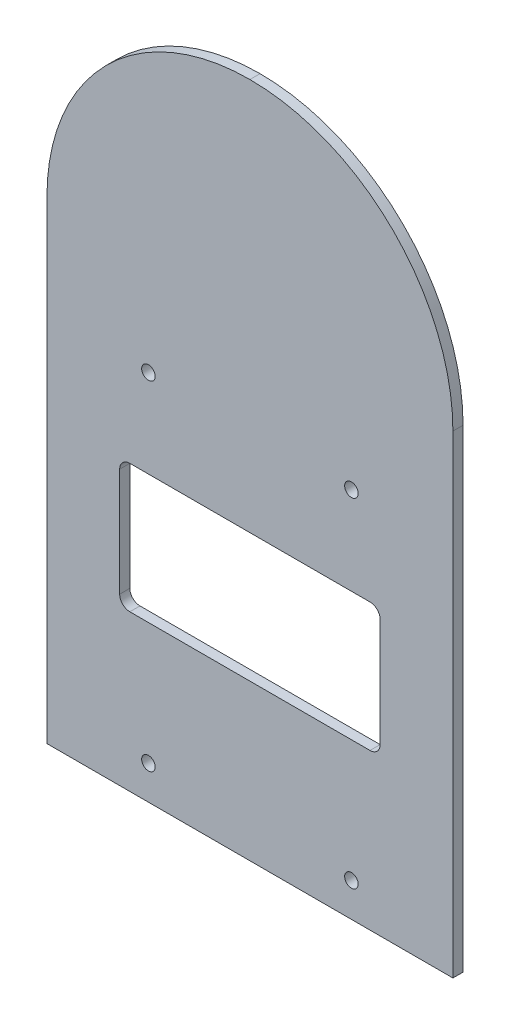
SolidWorks part; units mm, degrees
ref_plane "Front Plane" through (0, 0, 0) normal (0, 0, 1) x (1, 0, 0)
ref_plane "Top Plane" through (0, 0, 0) normal (0, 1, 0) x (1, 0, 0)
ref_plane "Right Plane" through (0, 0, 0) normal (1, 0, 0) x (0, 0, -1)
sketch "Sketch1" plane through (0, 0, 0) normal (0, 0, 1) x (1, 0, 0)
  line L1 (60, -100) -> (-60, -100)
  line L2 (60, -100) -> (60, 100)
  line L3 (60, 100) -> (-60, 100)
  line L4 (-60, -100) -> (-60, 100)
  line L5 (60, -100) -> (-60, 100) construction
  line L6 (60, 100) -> (-60, -100) construction
  point P0 (0, 0)
  dimension "D1" = 120
  dimension "D2" = 200
extrude "Boss-Extrude1" add sketch "Sketch1" along normal blind 3
fillet "Fillet1" radius 60 2 edges at (60, 100, 1.5) (-60, 100, 1.5)
sketch "Sketch2" plane through (0, 0, 3) normal (0, 0, 1) x (1, 0, 0)
  line L0 (-34.5, -17) -> (34.5, -17) construction
  line L1 (-35.5, -16) -> (35.5, -16)
  line L2 (-38.5, -19) -> (-38.5, -51)
  line L3 (-35.5, -54) -> (35.5, -54)
  line L4 (38.5, -19) -> (38.5, -51)
  line L5 (-34.5, -53) -> (34.5, -53) construction
  line L6 (-37.5, -46) -> (-37.5, -24) construction
  line L7 (37.5, -46) -> (37.5, -24) construction
  arc A0 (-38.5, -51) -> (-35.5, -54) centre (-35.5, -51) ccw
  arc A1 (35.5, -54) -> (38.5, -51) centre (35.5, -51) ccw
  arc A2 (38.5, -19) -> (35.5, -16) centre (35.5, -19) ccw
  arc A3 (-38.5, -19) -> (-35.5, -16) centre (-35.5, -19) cw
  dimension "D5" = 3
  dimension "D1" = 1
  dimension "D2" = 1
  dimension "D3" = 1
  dimension "D4" = 1
extrude "Cut-Extrude1" cut sketch "Sketch2" against normal blind 3
sketch "Sketch3" plane through (0, 0, 3) normal (0, 0, 1) x (1, 0, 0)
  line L0 (-60, 40) -> (-60, -100) construction
  line L1 (-60, -100) -> (60, -100) construction
  line L2 (0, -1.65) -> (0, 1.65) construction
  circle A0 centre (-30, -90) radius 2
  circle A1 centre (-30, 10) radius 2
  circle A2 centre (30, 10) radius 2
  circle A3 centre (30, -90) radius 2
  dimension "D1" = 30
  dimension "D2" = 10
extrude "Cut-Extrude2" cut sketch "Sketch3" against normal blind 10
